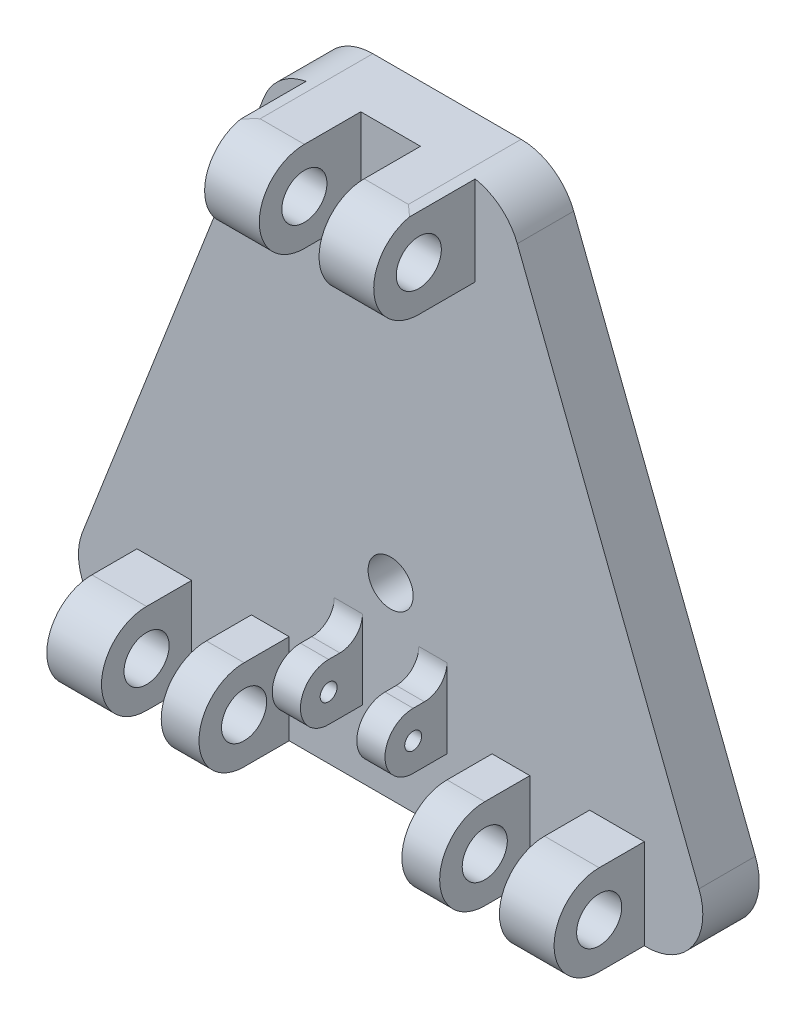
SolidWorks part; units mm, degrees
material "ABS"
ref_plane "Front Plane" through (0, 0, 0) normal (0, 0, 1) x (1, 0, 0)
ref_plane "Top Plane" through (0, 0, 0) normal (0, 1, 0) x (1, 0, 0)
ref_plane "Right Plane" through (0, 0, 0) normal (1, 0, 0) x (0, 0, -1)
sketch "Sketch1" plane through (0, 0, 0) normal (0, 0, 1) x (1, 0, 0)
  line L1 (-30, -28.625) -> (30, -28.625)
  line L2 (-30, -28.625) -> (-10, 22.875)
  line L3 (-10, 22.875) -> (10, 22.875)
  line L4 (30, -28.625) -> (10, 22.875)
  line L5 (-30, -28.625) -> (10, 22.875) construction
  line L6 (-10, 22.875) -> (30, -28.625) construction
  point P0 (0, 10)
  dimension "D1" = 51.5
  dimension "D2" = 60
  dimension "D3" = 20
  dimension "D4" = 10
extrude "Boss-Extrude1" add sketch "Sketch1" along normal mid plane 5
sketch "Sketch2" plane through (0, 0, 0) normal (1, 0, 0) x (0, 0, -1)
  line L0 (-2.5, -28.625) -> (-6.5, -28.625)
  line L1 (-2.5, -28.625) -> (-2.5, 22.875) construction
  line L2 (-6.5, -20.625) -> (-2.5, -20.625)
  line L3 (-2.5, -20.625) -> (-2.5, -28.625)
  line L4 (-2.5, -28.625) -> (2.5, -28.625) construction
  arc A0 (-6.5, -28.625) -> (-6.5, -20.625) centre (-6.5, -24.625) cw
  circle A1 centre (-6.5, -24.625) radius 2
  dimension "D1" = 4
  dimension "D2" = 4
  dimension "D3" = 4
extrude "Boss-Extrude2" add sketch "Sketch2" along normal mid plane 45
sketch "Sketch3" plane through (0, -28.625, 0) normal (0, -1, 0) x (1, 0, 0)
  line L0 (22.5, 10.5) -> (-22.5, 10.5) construction
  line L1 (-9, 18.5) -> (9, 18.5)
  line L2 (-9, 18.5) -> (-9, 2.5)
  line L3 (-9, 2.5) -> (9, 2.5)
  line L4 (9, 18.5) -> (9, 2.5)
  line L5 (-9, 18.5) -> (9, 2.5) construction
  line L6 (-9, 2.5) -> (9, 18.5) construction
  line L7 (22.5, 2.5) -> (30, 2.5) construction
  line L8 (22.5, 10.5) -> (-22.5, 10.5) construction
  line L9 (-17.65, 18.5) -> (-12.35, 18.5)
  line L10 (-17.65, 18.5) -> (-17.65, 2.5)
  line L11 (-17.65, 2.5) -> (-12.35, 2.5)
  line L12 (-12.35, 18.5) -> (-12.35, 2.5)
  line L13 (-17.65, 18.5) -> (-12.35, 2.5) construction
  line L14 (-17.65, 2.5) -> (-12.35, 18.5) construction
  point P0 (0, 10.5)
  point P9 (-15, 10.5)
  dimension "D1" = 18
  dimension "D2" = 5.3
  dimension "D3" = 15
extrude "Cut-Extrude1" cut sketch "Sketch3" against normal up to surface (28.625 mm away) up to plane "Top Plane"
mirror "Mirror2" about plane through (0, 0, 0) normal (1, 0, 0) of "Cut-Extrude1"
mirror "Mirror1" [suppressed] about plane through (0, 0, 0) normal (0, 1, 0)
sketch "Sketch7" plane through (0, 0, 0) normal (1, 0, 0) x (0, 0, -1)
  line L0 (-2.5, 14.875) -> (-7.5, 14.875)
  line L1 (-2.5, -28.625) -> (-2.5, 22.875) construction
  line L2 (-7.5, 22.875) -> (-2.5, 22.875)
  line L3 (-2.5, 22.875) -> (-2.5, 14.875)
  line L4 (-2.5, 22.875) -> (2.5, 22.875) construction
  arc A0 (-7.5, 14.875) -> (-7.5, 22.875) centre (-7.5, 18.875) cw
  circle A1 centre (-7.5, 18.875) radius 2
  dimension "D1" = 4
  dimension "D2" = 4
  dimension "D3" = 5
extrude "Boss-Extrude4" add sketch "Sketch7" along normal mid plane 15
sketch "Sketch8" plane through (0, 22.875, 0) normal (0, 1, 0) x (1, 0, 0)
  line L0 (-7.5, -11.5) -> (7.5, -11.5) construction
  line L1 (-2.65, -20.5) -> (2.65, -20.5)
  line L2 (-2.65, -20.5) -> (-2.65, -2.5)
  line L3 (-2.65, -2.5) -> (2.65, -2.5)
  line L4 (2.65, -20.5) -> (2.65, -2.5)
  line L5 (-2.65, -20.5) -> (2.65, -2.5) construction
  line L6 (-2.65, -2.5) -> (2.65, -20.5) construction
  line L7 (10, -2.5) -> (7.5, -2.5) construction
  point P0 (0, -11.5)
  dimension "D1" = 5.3
extrude "Cut-Extrude4" cut sketch "Sketch8" against normal up to surface (8 mm away) up to face at (0, 14.875, 5)
sketch "Sketch4" plane through (0, 0, 0) normal (1, 0, 0) x (0, 0, -1)
  line L0 (-2.5, -22.625) -> (-5.5, -22.625)
  line L1 (-2.5, -28.625) -> (-2.5, 22.875) construction
  line L2 (-5.5, -17.625) -> (-2.5, -17.625)
  line L3 (-2.5, -17.625) -> (-2.5, -22.625)
  line L5 (-2.5, -28.625) -> (2.5, -28.625) construction
  arc A0 (-5.5, -22.625) -> (-5.5, -17.625) centre (-5.5, -20.125) cw
  circle A1 centre (-5.5, -20.125) radius 0.75
  dimension "D1" = 1.5
  dimension "D2" = 2.5
  dimension "D3" = 3
  dimension "D4" = 6
extrude "Boss-Extrude3" add sketch "Sketch4" along normal mid plane 10
sketch "Sketch5" plane through (0, -17.625, 0) normal (0, 1, 0) x (1, 0, 0)
  line L0 (-5, -8) -> (5, -8) construction
  line L1 (-2.5, -13.5) -> (2.5, -13.5)
  line L2 (-2.5, -13.5) -> (-2.5, -2.5)
  line L3 (-2.5, -2.5) -> (2.5, -2.5)
  line L4 (2.5, -13.5) -> (2.5, -2.5)
  line L5 (-2.5, -13.5) -> (2.5, -2.5) construction
  line L6 (-2.5, -2.5) -> (2.5, -13.5) construction
  line L8 (10, -2.5) -> (7.5, -2.5) construction
  point P0 (0, -8)
  dimension "D1" = 5
extrude "Cut-Extrude2" cut sketch "Sketch5" against normal through all
fillet "Fillet1" [suppressed] radius 3
fillet "Fillet2" radius 2 2 edges at (3.75, -17.625, 2.5) (-3.75, -17.625, 2.5)
sketch "Sketch6" plane through (0, 0, 2.5) normal (0, 0, 1) x (1, 0, 0)
  circle A0 centre (0, -12) radius 2
  dimension "D1" = 4
  dimension "D2" = 12
extrude "Cut-Extrude3" cut sketch "Sketch6" against normal through all
fillet "Fillet4" radius 5 4 edges at (30, -28.625, 0) (-30, -28.625, 0) (10, 22.875, 0) (-10, 22.875, 0)
